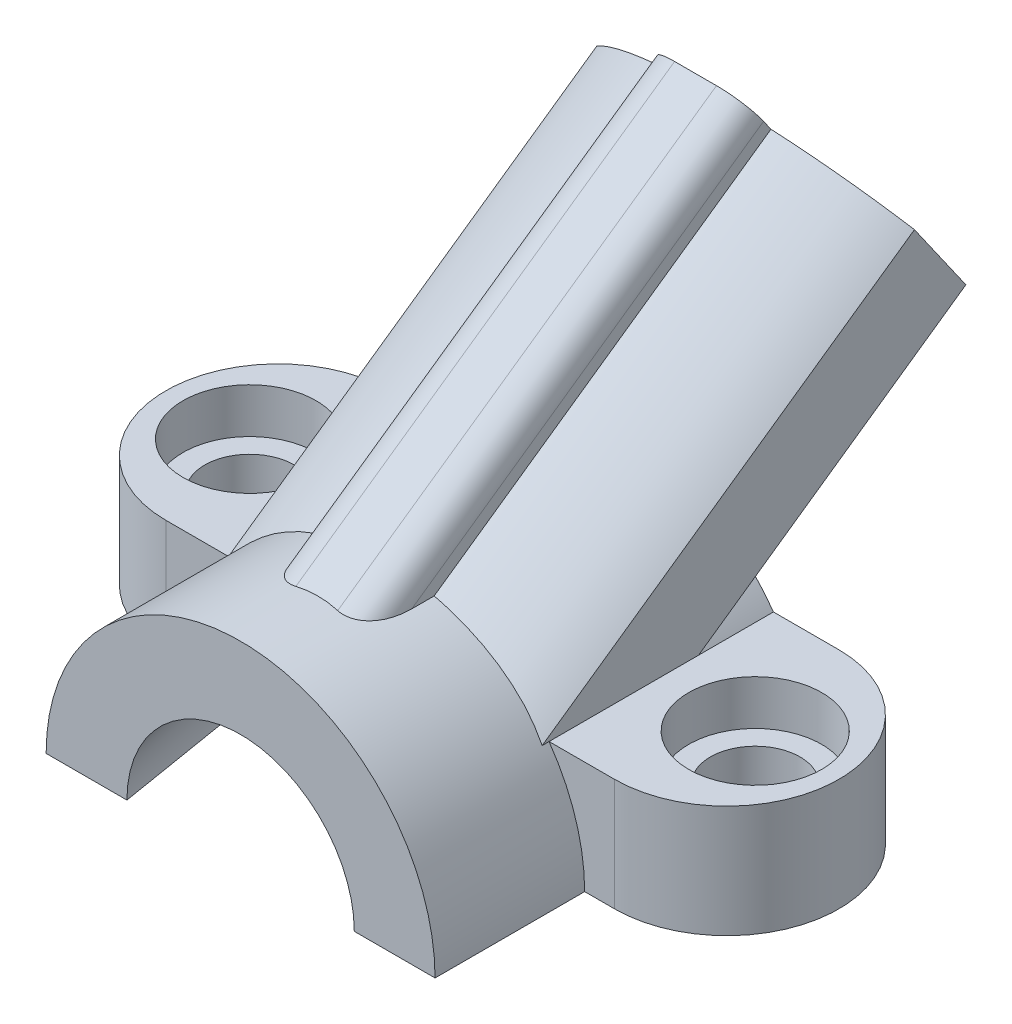
SolidWorks part; units mm, degrees
material "Thornel Mat VMA"
ref_plane "Front Plane" through (0, 0, 0) normal (0, 0, 1) x (1, 0, 0)
ref_plane "Top Plane" through (0, 0, 0) normal (0, 1, 0) x (1, 0, 0)
ref_plane "Right Plane" through (0, 0, 0) normal (1, 0, 0) x (0, 0, -1)
sketch "Sketch1" plane through (0, 0, 0) normal (0, 0, 1) x (1, 0, 0)
  circle A0 centre (0, 0) radius 13
  dimension "D1" = 26
extrude "Boss-Extrude1" add sketch "Sketch1" against normal blind 25
sketch "Sketch2" plane through (0, 0, 0) normal (1, 0, 0) x (0, 0, -1)
  line L0 (0, 0) -> (0, 7.6)
  line L1 (0, 13) -> (0, -13) construction
  line L2 (0, 7.6) -> (11.5, 9.5)
  line L3 (11.5, 9.5) -> (14, 10.6)
  line L5 (25, -13) -> (25, 13) construction
  line L6 (25, 11) -> (25, 0)
  line L7 (25, 0) -> (0, 0)
  line L8 (14, 10.6) -> (25, 11)
  dimension "D1" = 7.6
  dimension "D2" = 9.5
  dimension "D3" = 10.6
  dimension "D4" = 11
  dimension "D5" = 11
  dimension "D6" = 13.5
revolve "Cut-Revolve1" cut sketch "Sketch2" angle 360 about L7
sketch "Sketch3" plane through (0, 0, 0) normal (0, 1, 0) x (1, 0, 0)
  line L0 (-13, 25) -> (-13, 10)
  line L1 (-13, 25) -> (-13, 0) construction
  line L2 (-13, 10) -> (-15, 10)
  line L3 (-13, 25) -> (-15, 25)
  line L4 (0, 0) -> (0, 26.1438) construction
  line L8 (13, 25) -> (15, 25)
  line L9 (13, 10) -> (15, 10)
  line L10 (13, 25) -> (13, 10)
  arc A0 (-15, 10) -> (-15, 25) centre (-15, 17.5) cw
  arc A2 (15, 10) -> (15, 25) centre (15, 17.5) ccw
  dimension "D1" = 15
  dimension "D2" = 2
extrude "Boss-Extrude2" add sketch "Sketch3" along normal mid plane 15
sketch "Sketch4" plane through (0, 0, -25) normal (0, 0, -1) x (-1, 0, 0)
  line L11 (-13, 7.5) -> (-13, -7.5)
  line L12 (-13, -7.5) -> (-8.0467, -7.5)
  line L14 (13, 7.5) -> (13, -7.5)
  line L20 (-8.0467, 7.5) -> (-13, 7.5)
  line L21 (13, -7.5) -> (8.0467, -7.5)
  line L23 (8.0467, 7.5) -> (13, 7.5)
  arc A6 (-8.0467, 7.5) -> (-8.0467, -7.5) centre (0, 0) ccw
  circle A7 centre (0, 0) radius 11 construction
  arc A9 (8.0467, -7.5) -> (8.0467, 7.5) centre (0, 0) ccw
extrude "Boss-Extrude3" add sketch "Sketch4" against normal blind 15
sketch "Sketch5" plane through (0, 7.5, 0) normal (0, 1, 0) x (1, 0, 0)
  circle A2 centre (16.9, 17.5) radius 3
  arc A7 (15, 10) -> (15, 25) centre (15, 17.5) ccw construction
  circle A8 centre (-16.9, 17.5) radius 3
  arc A9 (-15, 25) -> (-15, 10) centre (-15, 17.5) ccw construction
  point P10 (22.5, 17.5)
  point P11 (-22.5, 17.5)
  dimension "D1" = 6
  dimension "D2" = 5.6
  dimension "D3" = 5.6
extrude "Cut-Extrude1" cut sketch "Sketch5" against normal through all
sketch "Sketch6" plane through (0, 7.5, 0) normal (0, 1, 0) x (1, 0, 0)
  circle A0 centre (-16.9, 17.5) radius 4.45
  circle A1 centre (16.9, 17.5) radius 4.45
  circle A2 centre (-16.9, 17.5) radius 3 construction
  circle A3 centre (16.9, 17.5) radius 3 construction
  dimension "D1" = 8.9
extrude "Cut-Extrude2" cut sketch "Sketch6" against normal blind 3
sketch "Sketch7" plane through (0, -7.5, 0) normal (0, -1, 0) x (1, 0, 0)
  circle A0 centre (-16.9, -17.5) radius 4
  circle A1 centre (16.9, -17.5) radius 4
  circle A2 centre (-16.9, -17.5) radius 3 construction
  dimension "D1" = 8
extrude "Cut-Extrude3" cut sketch "Sketch7" against normal blind 7.5
sketch "Sketch8" plane through (0, 0, 0) normal (0, 1, 0) x (1, 0, 0)
  point P0 (0, 25.7)
  dimension "D1" = 25.7
ref_plane "Plane1" through (0, 7.1659, -10.2339) normal (0, 0.5736, -0.8192) x (1, 0, 0)
ref_plane "Plane2" through (0, 24.3732, -34.8085) normal (0, 0.5736, -0.8192) x (1, 0, 0)
ref_axis "Axis1" through (0, 0, -25.7) along (0, 0.5736, -0.8192)
sketch "Sketch9" plane through (0, 24.3732, -34.8085) normal (0, 0.5736, -0.8192) x (1, 0, 0)
  line L0 (-10.62, 5.324) -> (10.62, 5.324)
  line L1 (-10.62, 5.324) -> (-10.62, -0.6699)
  line L2 (10.62, 5.324) -> (10.62, -0.6699)
  line L3 (-21.2787, 0) -> (21.2787, 0) construction
  line L4 (-1.4, -7.666) -> (1.4, -7.666)
  line L6 (3.4, -4.8074) -> (3.4, -5.666)
  line L7 (-3.4, -4.8074) -> (-3.4, -5.666)
  arc A0 (-10.62, -0.6699) -> (-3.4, -4.8074) centre (0, 9.494) ccw
  arc A1 (3.4, -4.8074) -> (10.62, -0.6699) centre (0, 9.494) ccw
  arc A2 (-3.4, -5.666) -> (-1.4, -7.666) centre (-1.4, -5.666) ccw
  arc A3 (1.4, -7.666) -> (3.4, -5.666) centre (1.4, -5.666) ccw
  point P0 (0, 9.494)
  point P5 (0, 5.324)
  point P12 (0, 0)
  dimension "D3" = 14.7
  dimension "D9" = 2
  dimension "D1" = 21.24
  dimension "D2" = 4.17
  dimension "D4" = 5.324
  dimension "D5" = 12.99
  dimension "D7" = 3.4
  dimension "D8" = 6.8
extrude "Boss-Extrude6" add sketch "Sketch9" against normal up to next
sketch "Sketch10" plane through (0, 24.3732, -34.8085) normal (0, 0.5736, -0.8192) x (-1, 0, 0)
  line L0 (-10.62, -5.324) -> (10.62, -5.324) construction
  line L1 (-10.62, 0.6699) -> (-10.62, -5.324) construction
  circle A0 centre (-4, -0.484) radius 1.6
  circle A1 centre (4, -0.484) radius 1.6
  dimension "D3" = 6.62
  dimension "D4" = 3.2
  dimension "D1" = 4.84
  dimension "D2" = 8
extrude "Cut-Extrude4" cut sketch "Sketch10" against normal through all
ref_plane "Plane3" through (0, 18.6374, -26.617) normal (0, 0.5736, -0.8192) x (1, 0, 0)
sketch "Sketch11" plane through (0, 18.6374, -26.617) normal (0, 0.5736, -0.8192) x (1, 0, 0)
  circle A0 centre (4, 0.484) radius 3.1
  circle A1 centre (-4, 0.484) radius 3.1
  circle A2 centre (-4, 0.484) radius 1.6 construction
  circle A3 centre (4, 0.484) radius 1.6 construction
  dimension "D1" = 6.2
extrude "Cut-Extrude5" cut sketch "Sketch11" against normal through all
sketch "Sketch12" plane through (0, 0, 0) normal (0, 1, 0) x (1, 0, 0)
  line L0 (0, 0) -> (0, 55.5084) construction
  line L1 (-25, 39.0176) -> (25, 39.0176)
  line L2 (-25, 39.0176) -> (-25, -10.9824)
  line L3 (-25, -10.9824) -> (25, -10.9824)
  line L4 (25, 39.0176) -> (25, -10.9824)
  dimension "D1" = 50
  dimension "D2" = 50
  dimension "D3" = 25
extrude "Cut-Extrude8" cut sketch "Sketch12" against normal through all
equation "\"D8@Sketch9\" = \"D7@Sketch9\" * 2"
equation "\"D3@Sketch5\" = \"D2@Sketch5\""
